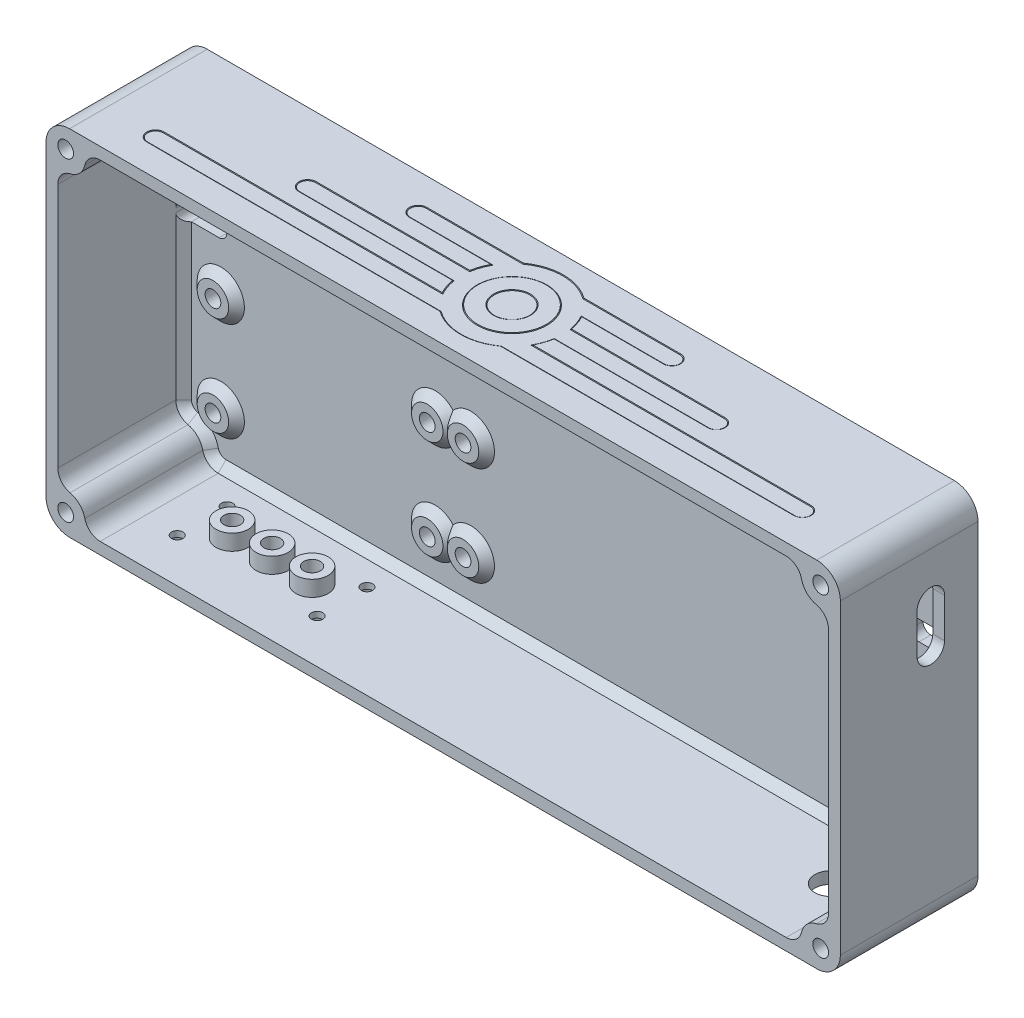
SolidWorks part; units mm, degrees
ref_plane "Plan de face" through (0, 0, 0) normal (0, 0, 1) x (1, 0, 0)
ref_plane "Plan de dessus" through (0, 0, 0) normal (0, 1, 0) x (1, 0, 0)
ref_plane "Plan de droite" through (0, 0, 0) normal (1, 0, 0) x (0, 0, -1)
sketch "Esquisse1" plane through (0, 0, 0) normal (0, 0, 1) x (1, 0, 0)
  line L1 (-95, 45) -> (95, 45)
  line L2 (-101, 39) -> (-101, -39)
  line L3 (-95, -45) -> (95, -45)
  line L4 (101, 39) -> (101, -39)
  line L5 (-101, 45) -> (101, -45) construction
  line L6 (-101, -45) -> (101, 45) construction
  line L7 (96, -40) -> (-96, -40) construction
  line L8 (96, -40) -> (96, 40) construction
  line L9 (96, 40) -> (-96, 40) construction
  line L10 (-96, -40) -> (-96, 40) construction
  line L11 (96, -40) -> (-96, 40) construction
  line L12 (96, 40) -> (-96, -40) construction
  arc A0 (95, -45) -> (101, -39) centre (95, -39) ccw
  arc A1 (95, 45) -> (101, 39) centre (95, 39) cw
  arc A2 (-101, -39) -> (-95, -45) centre (-95, -39) ccw
  arc A3 (-95, 45) -> (-101, 39) centre (-95, 39) ccw
  circle A4 centre (-96, 40) radius 2
  circle A5 centre (-96, -40) radius 2
  circle A6 centre (96, 40) radius 2
  circle A7 centre (96, -40) radius 2
  point P0 (0, 0)
  point P18 (0, 0)
  dimension "D3" = 6
  dimension "D6" = 4
  dimension "D1" = 202
  dimension "D2" = 90
  dimension "D4" = 192
  dimension "D5" = 80
extrude "Boss.-Extru.1" add sketch "Esquisse1" along normal blind 35
shell "Coque1" thickness 3 removed face at (98, 40, 35)
sketch "Esquisse9" plane through (0, 0, 0) normal (0, 0, -1) x (-1, 0, 0)
  circle A0 centre (96, 40) radius 2 construction
  circle A1 centre (96, -40) radius 2 construction
  circle A2 centre (-96, -40) radius 2 construction
  circle A3 centre (-96, 40) radius 2 construction
  circle A4 centre (96, 40) radius 2
  circle A5 centre (96, -40) radius 2
  circle A6 centre (-96, -40) radius 2
  circle A7 centre (-96, 40) radius 2
extrude "Boss.-Extru.3" add sketch "Esquisse9" against normal offset from surface (25 mm away) 10 up to face at (0, 0, 35)
sketch "Esquisse2" plane through (0, 0, 3) normal (0, 0, 1) x (1, 0, 0)
  line L0 (91.4174, 42) -> (-91.4174, 42) construction
  line L1 (92.6, -33.9) -> (-29, -33.9) construction
  line L2 (92.6, -33.9) -> (92.6, 32) construction
  line L3 (92.6, 32) -> (-29, 32) construction
  line L4 (-29, -33.9) -> (-29, 32) construction
  line L5 (-30, -33.9) -> (-92.6, -33.9) construction
  line L6 (-30, -33.9) -> (-30, 32) construction
  line L7 (-30, 32) -> (-92.6, 32) construction
  line L8 (-92.6, -33.9) -> (-92.6, 32) construction
  line L9 (88.55, -29.4) -> (-24.95, -29.4) construction
  line L10 (88.55, -29.4) -> (88.55, -4.2) construction
  line L11 (88.55, -4.2) -> (-24.95, -4.2) construction
  line L12 (-24.95, -29.4) -> (-24.95, -4.2) construction
  line L13 (-34.05, -29.4) -> (-88.55, -29.4) construction
  line L14 (-34.05, -29.4) -> (-34.05, -4.2) construction
  line L15 (-34.05, -4.2) -> (-88.55, -4.2) construction
  line L16 (-88.55, -29.4) -> (-88.55, -4.2) construction
  line L17 (0, 0) -> (92.6, 32) construction
  line L20 (-92.6, 32) -> (0, 0) construction
  circle A0 centre (88.55, -29.4) radius 4
  circle A1 centre (88.55, -4.2) radius 4
  circle A2 centre (-24.95, -4.2) radius 4
  circle A3 centre (-24.95, -29.4) radius 4
  circle A4 centre (-34.05, -29.4) radius 4
  circle A5 centre (-34.05, -4.2) radius 4
  circle A6 centre (-88.55, -4.2) radius 4
  circle A7 centre (-88.55, -29.4) radius 4
  point P18 (31.8, -33.9)
  point P19 (31.8, -29.4)
  point P20 (-61.3, -33.9)
  point P21 (-61.3, -29.4)
  dimension "D9" = 8
  dimension "D1" = 121.6
  dimension "D2" = 1
  dimension "D3" = 62.6
  dimension "D4" = 25.2
  dimension "D5" = 113.5
  dimension "D6" = 54.5
  dimension "D7" = 4.5
  dimension "D8" = 65.9
  dimension "D10" = 10
extrude "Boss.-Extru.2" add sketch "Esquisse2" along normal blind 2
sketch "Esquisse3" plane through (0, 0, 5) normal (0, 0, 1) x (1, 0, 0)
  circle A0 centre (88.55, -29.4) radius 2
  circle A1 centre (88.55, -4.2) radius 2
  circle A2 centre (-24.95, -4.2) radius 2
  circle A3 centre (-24.95, -29.4) radius 2
  circle A4 centre (-34.05, -29.4) radius 2
  circle A5 centre (-88.55, -4.2) radius 2
  circle A6 centre (-88.55, -29.4) radius 2
  circle A7 centre (-34.05, -4.2) radius 2
  dimension "D1" = 4
extrude "Enlèv. mat.-Extru.1" cut sketch "Esquisse3" against normal through all
sketch "Esquisse4" plane through (0, -45, 0) normal (0, -1, 0) x (1, 0, 0)
  line L0 (81, 35) -> (81, 0) construction
  line L1 (-95, 35) -> (95, 35) construction
  line L2 (-95, 0) -> (95, 0) construction
  line L4 (-101, 35) -> (-101, 0) construction
  line L5 (-78.78, 23.85) -> (-43.22, 23.85) construction
  line L6 (-78.78, 23.85) -> (-78.78, 11.15) construction
  line L7 (-78.78, 11.15) -> (-43.22, 11.15) construction
  line L8 (-43.22, 23.85) -> (-43.22, 11.15) construction
  line L9 (-78.78, 23.85) -> (-43.22, 11.15) construction
  line L10 (-78.78, 11.15) -> (-43.22, 23.85) construction
  line L14 (101, 35) -> (101, 0) construction
  circle A0 centre (81, 17.5) radius 4
  circle A1 centre (-71.16, 17.5) radius 2.1
  circle A2 centre (-61, 17.5) radius 2.1
  circle A3 centre (-50.84, 17.5) radius 2.1
  point P10 (-61, 17.5)
  dimension "D1" = 8
  dimension "D5" = 4.2
  dimension "D2" = 20
  dimension "D3" = 35.56
  dimension "D4" = 12.7
  dimension "D7" = 40
  dimension "D8" = 17.5
  dimension "D6" = 3
extrude "Enlèv. mat.-Extru.2" cut sketch "Esquisse4" against normal up to next
hole_wizard "Chambrage pour vis à six pans creux M2.51" positions "Esquisse5" profile "Esquisse6" counterbore size "M2.5" standard "ISO" end condition up to next
sketch "Esquisse5" plane through (0, -45, 0) normal (0, -1, 0) x (-1, 0, 0)
  point P0 (78.78, -23.85)
  point P3 (78.78, -11.15)
  point P6 (43.22, -23.85)
  point P9 (43.22, -11.15)
sketch "Esquisse6" plane through (-78.78, -45, 23.85) normal (1, 0, 0) x (0, 0, -1)
  line L0 (0, 0) -> (0, 3)
  line L1 (0, 3) -> (1.45, 3)
  line L3 (1.45, 3) -> (1.45, 1.5)
  line L4 (1.45, 1.5) -> (2.75, 1.5)
  line L5 (2.75, 1.5) -> (2.75, 0)
  line L7 (2.75, 0) -> (0, 0)
  line L11 (0, -6.35) -> (0, 107.95) construction
  dimension "Diamètre du perçage jusqu'au prochain" = 2.9
  dimension "Profondeur du perçage jusqu'au prochain" = 3
  dimension "Diamètre du chambrage" = 5.5
  dimension "Profondeur du chambrage" = 1.5
sketch "Esquisse7" plane through (0, -42, 0) normal (0, 1, 0) x (1, 0, 0)
  circle A0 centre (-71.16, -17.5) radius 2.1 construction
  circle A1 centre (-61, -17.5) radius 2.1 construction
  circle A2 centre (-50.84, -17.5) radius 2.1 construction
  circle A3 centre (-71.16, -17.5) radius 2.1
  circle A4 centre (-61, -17.5) radius 2.1
  circle A5 centre (-50.84, -17.5) radius 2.1
extrude "Extru.-Mince1" add sketch "Esquisse7" along normal blind 4 thin thin type one direction wall 2
fillet "Congé1" radius 4 8 edges at (-91.4174, -42, 19) (-98, -35.4174, 19) (91.4174, -42, 19) (98, -35.4174, 19) (98, 35.4174, 19) (91.4174, 42, 19) (-91.4174, 42, 19) (-98, 35.4174, 19)
chamfer "Chanfrein1" distance 2 angle 45 24 edges at (92.4645, -36.4645, 3) (0, -42, 3) (-92.4645, -36.4645, 3) (-98, 0, 3) (-92.4645, 36.4645, 3) (0, 42, 3) (92.4645, 36.4645, 3) (98, 0, 3) (92.55, -4.2, 3) (-20.95, -4.2, 3) (-20.95, -29.4, 3) (92.55, -29.4, 3) (-30.05, -29.4, 3) (-30.05, -4.2, 3) (-84.55, -4.2, 3) (-84.55, -29.4, 3) (-97.1269, -33.7195, 3) (-97.1269, 33.7195, 3) (-89.7195, 41.1269, 3) (89.7195, 41.1269, 3) (97.1269, 33.7195, 3) (97.1269, -33.7195, 3) (89.7195, -41.1269, 3) (-89.7195, -41.1269, 3)
sketch "Esquisse11" plane through (0, 0, 0) normal (0, 0, -1) x (-1, 0, 0)
  line L0 (-95, 45) -> (95, 45) construction
  line L1 (81, -25) -> (-81, -25) construction
  line L2 (81, -25) -> (81, 25) construction
  line L3 (81, 25) -> (-81, 25) construction
  line L4 (-81, -25) -> (-81, 25) construction
  line L5 (81, -25) -> (-81, 25) construction
  line L6 (81, 25) -> (-81, -25) construction
  line L7 (-83.6, 22.4) -> (-78.4, 22.4)
  line L8 (-83.6, 22.4) -> (-83.6, 27.6)
  line L9 (-83.6, 27.6) -> (-78.4, 27.6)
  line L10 (-78.4, 22.4) -> (-78.4, 27.6)
  line L11 (-83.6, 22.4) -> (-78.4, 27.6) construction
  line L12 (-83.6, 27.6) -> (-78.4, 22.4) construction
  line L13 (-83.6, -22.4) -> (-78.4, -22.4)
  line L14 (-83.6, -22.4) -> (-83.6, -27.6)
  line L15 (-83.6, -27.6) -> (-78.4, -27.6)
  line L16 (-78.4, -22.4) -> (-78.4, -27.6)
  line L17 (-83.6, -22.4) -> (-78.4, -27.6) construction
  line L18 (-83.6, -27.6) -> (-78.4, -22.4) construction
  line L19 (78.4, -22.4) -> (83.6, -22.4)
  line L20 (78.4, -22.4) -> (78.4, -27.6)
  line L21 (78.4, -27.6) -> (83.6, -27.6)
  line L22 (83.6, -22.4) -> (83.6, -27.6)
  line L23 (78.4, -22.4) -> (83.6, -27.6) construction
  line L24 (78.4, -27.6) -> (83.6, -22.4) construction
  line L25 (78.4, 27.6) -> (83.6, 27.6)
  line L26 (78.4, 27.6) -> (78.4, 22.4)
  line L27 (78.4, 22.4) -> (83.6, 22.4)
  line L28 (83.6, 27.6) -> (83.6, 22.4)
  line L29 (78.4, 27.6) -> (83.6, 22.4) construction
  line L30 (78.4, 22.4) -> (83.6, 27.6) construction
  line L31 (-101, -39) -> (-101, 39) construction
  point P0 (0, 0)
  dimension "D1" = 5.2
  dimension "D2" = 20
  dimension "D3" = 20
extrude "Enlèv. mat.-Extru.5" cut sketch "Esquisse11" against normal blind 2.5
sketch "Esquisse8" plane through (0, 0, 0) normal (0, 0, -1) x (-1, 0, 0)
  line L1 (-98, 42) -> (98, 42)
  line L2 (-98, 42) -> (-98, 31)
  line L3 (-98, 31) -> (98, 31)
  line L4 (98, 42) -> (98, 31)
  line L5 (-98, 42) -> (98, 31) construction
  line L6 (-98, 31) -> (98, 42) construction
  line L7 (-98, -35.4174) -> (-98, 44.5826) construction
  line L8 (98, 35.4174) -> (98, -44.5826) construction
  line L9 (87.225, 42) -> (-87.225, 42) construction
  line L11 (-98, 31) -> (-87, 31)
  line L12 (-98, 31) -> (-98, 8)
  line L13 (-98, 8) -> (-87, 8)
  line L14 (-87, 31) -> (-87, 8)
  line L15 (98, 31) -> (87, 31)
  line L16 (98, 31) -> (98, 8)
  line L17 (98, 8) -> (87, 8)
  line L18 (87, 31) -> (87, 8)
  point P0 (0, 36.5)
  dimension "D1" = 23
  dimension "D2" = 11
extrude "Enlèv. mat.-Extru.3" cut sketch "Esquisse8" against normal blind 2 contours L14 L3 L12 L13 | L4 L1 L2 L3 | L3 L18 L17 L16 region at (0, 36.5, 0) region at (92.5, 19.5, 0) region at (-92.5, 19.5, 0)
sketch "Esquisse10" plane through (0, 0, 2) normal (0, 0, -1) x (-1, 0, 0)
  line L10 (-87, 31) -> (-87, 8) construction
  line L11 (-98, 8) -> (-87, 8)
  line L12 (-98, 8) -> (-98, 13)
  line L13 (-98, 13) -> (-87, 13)
  line L14 (-87, 8) -> (-87, 13)
  line L15 (87, 31) -> (87, 8) construction
  line L16 (98, 8) -> (87, 8)
  line L17 (98, 8) -> (98, 13)
  line L18 (98, 13) -> (87, 13)
  line L19 (87, 8) -> (87, 13)
  dimension "D1" = 5
extrude "Enlèv. mat.-Extru.4" cut sketch "Esquisse10" against normal up to next
fillet "Congé2" radius 2 12 edges at (-98, 8, 2.5) (-98, 13, 3.5) (-87, 13, 2.5) (-87, 8, 1.5) (-87, 31, 1) (-98, 42, 1) (98, 8, 2.5) (98, 13, 3.5) (87, 13, 2.5) (98, 42, 1) (87, 8, 1.5) (87, 31, 1)
sketch "Esquisse15" plane through (0, 45, 0) normal (0, 1, 0) x (1, 0, 0)
  line L0 (0, 0) -> (0, -35) construction
  line L1 (95, 0) -> (-95, 0) construction
  line L2 (95, -35) -> (-95, -35) construction
  line L3 (-8.7, -17.5) -> (-51.9785, -17.5) construction
  line L4 (-8.7, -19.7) -> (-51.9785, -19.7)
  line L5 (-8.7, -15.3) -> (-51.9785, -15.3)
  line L6 (-2.265, -9.1) -> (-32.265, -9.1) construction
  line L7 (-2.265, -11.3) -> (-32.265, -11.3)
  line L8 (-2.265, -6.9) -> (-32.265, -6.9)
  line L9 (-2.265, -25.9) -> (-82.265, -25.9) construction
  line L10 (-2.265, -28.1) -> (-82.265, -28.1)
  line L11 (-2.265, -23.7) -> (-82.265, -23.7)
  circle A0 centre (0, -17.5) radius 4.7
  circle A1 centre (0, -17.5) radius 8.7
  circle A2 centre (0, -17.5) radius 13.1
  arc A3 (-8.7, -19.7) -> (-8.7, -15.3) centre (-8.7, -17.5) ccw
  arc A4 (-51.9785, -15.3) -> (-51.9785, -19.7) centre (-51.9785, -17.5) ccw
  arc A5 (-2.265, -11.3) -> (-2.265, -6.9) centre (-2.265, -9.1) ccw
  arc A6 (-32.265, -6.9) -> (-32.265, -11.3) centre (-32.265, -9.1) ccw
  arc A7 (-2.265, -28.1) -> (-2.265, -23.7) centre (-2.265, -25.9) ccw
  arc A8 (-82.265, -23.7) -> (-82.265, -28.1) centre (-82.265, -25.9) ccw
  arc A15 (-32.265, -9.1) -> (-82.265, -25.9) centre (-120.4091, 170.4289) cw construction
  point P14 (-30.3393, -17.5)
  point P19 (-17.265, -9.1)
  point P26 (-42.265, -25.9)
  dimension "D2" = 9.4
  dimension "D3" = 4
  dimension "D4" = 4.4
  dimension "D5" = 2.2
  dimension "D9" = 200
  dimension "D1" = 8.4
  dimension "D6" = 8.4
  dimension "D7" = 30
  dimension "D8" = 80
extrude "Enlèv. mat.-Extru.7" cut sketch "Esquisse15" against normal blind 1.6 contours A7 L10 A2 L8 A5 A1 | L10 A7 A1 L11 A2 | L11 A8 L10 A2 | A3 L4 A2 L11 A1 | L5 A4 L4 A2 | L4 A3 A1 L5 A2 | A3 A1 L7 A2 L5 | A1 A5 L8 A2 L7 | L8 A6 L7 A2 | A0 region at (-9.8958, 45, 21.7619) region at (-10.8222, 45, 17.5) region at (-33.3752, 45, 17.5) region at (-9.8958, 45, 13.2381) region at (-46.9456, 45, 25.9187) region at (-6.0605, 45, 26.0393) region at (-6.0605, 45, 8.9607) region at (-21.9321, 45, 9.0425) region at (-4.9812, 45, 28.4345) region at (0, 45, 17.5)
mirror "Symétrie1" about plane through (0, 0, 0) normal (1, 0, 0) of "Enlèv. mat.-Extru.7"
sketch "Esquisse16" plane through (0, 43.4, 0) normal (0, 1, 0) x (1, 0, 0)
  line L25 (-11.2004, -23.9) -> (-82.265, -23.9)
  line L26 (-82.265, -27.9) -> (-7.6322, -27.9)
  line L27 (7.6322, -27.9) -> (82.265, -27.9)
  line L28 (82.265, -23.9) -> (11.2004, -23.9)
  line L29 (12.744, -19.5) -> (51.9785, -19.5)
  line L30 (51.9785, -15.5) -> (12.744, -15.5)
  line L31 (11.2004, -11.1) -> (32.265, -11.1)
  line L32 (32.265, -7.1) -> (7.6322, -7.1)
  line L33 (-7.6322, -7.1) -> (-32.265, -7.1)
  line L34 (-32.265, -11.1) -> (-11.2004, -11.1)
  line L35 (-12.744, -15.5) -> (-51.9785, -15.5)
  line L36 (-51.9785, -19.5) -> (-12.744, -19.5)
  line L37 (-11.2004, -23.9) -> (-82.265, -23.9)
  line L38 (-82.265, -27.9) -> (-7.6322, -27.9)
  line L39 (7.6322, -27.9) -> (82.265, -27.9)
  line L40 (82.265, -23.9) -> (11.2004, -23.9)
  line L41 (12.744, -19.5) -> (51.9785, -19.5)
  line L42 (51.9785, -15.5) -> (12.744, -15.5)
  line L43 (11.2004, -11.1) -> (32.265, -11.1)
  line L44 (32.265, -7.1) -> (7.6322, -7.1)
  line L45 (-7.6322, -7.1) -> (-32.265, -7.1)
  line L46 (-32.265, -11.1) -> (-11.2004, -11.1)
  line L47 (-12.744, -15.5) -> (-51.9785, -15.5)
  line L48 (-51.9785, -19.5) -> (-12.744, -19.5)
  circle A16 centre (0, -17.5) radius 8.9
  circle A17 centre (0, -17.5) radius 8.9
  circle A19 centre (0, -17.5) radius 4.5
  circle A20 centre (0, -17.5) radius 4.5
  arc A26 (-12.744, -19.5) -> (-11.2004, -23.9) centre (0, -17.5) ccw
  arc A27 (-82.265, -23.9) -> (-82.265, -27.9) centre (-82.265, -25.9) ccw
  arc A28 (-7.6322, -27.9) -> (7.6322, -27.9) centre (0, -17.5) ccw
  arc A29 (82.265, -27.9) -> (82.265, -23.9) centre (82.265, -25.9) ccw
  arc A30 (11.2004, -23.9) -> (12.744, -19.5) centre (0, -17.5) ccw
  arc A31 (51.9785, -19.5) -> (51.9785, -15.5) centre (51.9785, -17.5) ccw
  arc A32 (12.744, -15.5) -> (11.2004, -11.1) centre (0, -17.5) ccw
  arc A33 (32.265, -11.1) -> (32.265, -7.1) centre (32.265, -9.1) ccw
  arc A34 (7.6322, -7.1) -> (-7.6322, -7.1) centre (0, -17.5) ccw
  arc A35 (-32.265, -7.1) -> (-32.265, -11.1) centre (-32.265, -9.1) ccw
  arc A36 (-11.2004, -11.1) -> (-12.744, -15.5) centre (0, -17.5) ccw
  arc A37 (-51.9785, -15.5) -> (-51.9785, -19.5) centre (-51.9785, -17.5) ccw
  arc A38 (-12.744, -19.5) -> (-11.2004, -23.9) centre (0, -17.5) ccw
  arc A39 (-82.265, -23.9) -> (-82.265, -27.9) centre (-82.265, -25.9) ccw
  arc A40 (-7.6322, -27.9) -> (7.6322, -27.9) centre (0, -17.5) ccw
  arc A41 (82.265, -27.9) -> (82.265, -23.9) centre (82.265, -25.9) ccw
  arc A42 (11.2004, -23.9) -> (12.744, -19.5) centre (0, -17.5) ccw
  arc A43 (51.9785, -19.5) -> (51.9785, -15.5) centre (51.9785, -17.5) ccw
  arc A44 (12.744, -15.5) -> (11.2004, -11.1) centre (0, -17.5) ccw
  arc A45 (32.265, -11.1) -> (32.265, -7.1) centre (32.265, -9.1) ccw
  arc A46 (7.6322, -7.1) -> (-7.6322, -7.1) centre (0, -17.5) ccw
  arc A47 (-32.265, -7.1) -> (-32.265, -11.1) centre (-32.265, -9.1) ccw
  arc A48 (-11.2004, -11.1) -> (-12.744, -15.5) centre (0, -17.5) ccw
  arc A49 (-51.9785, -15.5) -> (-51.9785, -19.5) centre (-51.9785, -17.5) ccw
  dimension "D1" = 0.2
  dimension "D2" = 0.2
  dimension "D3" = 0.2
extrude "Boss.-Extru.6" add sketch "Esquisse16" along normal blind 1.5 separate body contours L47 A49 L48 A38 L37 A39 L38 A40 L39 A41 L40 A42 L41 A43 L42 A44 L43 A45 L44 A46 L45 A47 L46 A48 A17 | A20 region at (-10.5639, 43.4, 21.2059) region at (0, 43.4, 17.5)
sketch "Esquisse17" plane through (0, 42, 0) normal (0, -1, 0) x (1, 0, 0)
  line L0 (-6.2, 23.7) -> (6.2, 23.7)
  line L1 (-6, 23.5) -> (6, 23.5) construction
  line L2 (-6, 23.5) -> (-6, 11.5) construction
  line L3 (-6, 11.5) -> (6, 11.5) construction
  line L4 (6, 23.5) -> (6, 11.5) construction
  line L5 (-6, 23.5) -> (6, 11.5) construction
  line L6 (-6, 11.5) -> (6, 23.5) construction
  line L7 (6.2, 23.7) -> (6.2, 11.3)
  line L8 (-6.2, 11.3) -> (6.2, 11.3)
  line L9 (-6.2, 23.7) -> (-6.2, 11.3)
  line L10 (-8.2, 25.7) -> (8.2, 25.7)
  line L11 (8.2, 25.7) -> (8.2, 9.3)
  line L12 (-8.2, 9.3) -> (8.2, 9.3)
  line L13 (-8.2, 25.7) -> (-8.2, 9.3)
  circle A0 centre (0, 17.5) radius 4.7 construction
  circle A1 centre (0, 17.5) radius 3.5 construction
  circle A2 centre (0, 17.5) radius 3.9
  point P0 (0, 17.5)
  dimension "D2" = 7
  dimension "D1" = 12
  dimension "D3" = 0.2
  dimension "D4" = 2
  dimension "D5" = 0.4
extrude "Boss.-Extru.7" add sketch "Esquisse17" along normal blind 2.3 contours L0 L9 L8 L7 A2 | L10 L13 L12 L11 L9 L0 L7 L8 region at (0, 42, 23.5246) region at (0, 42, 25.4681)
extrude "Boss.-Extru.8" add sketch "Esquisse17<3>" along normal blind 3 from surface contours L10 L13 L12 L11 L9 L0 L7 L8 region at (0, 42, 25.4681) starting at face at (0, 39.7, 13.6)
sketch "Esquisse17<3>" plane through (0, 42, 0) normal (0, -1, 0) x (1, 0, 0) same geometry as "Esquisse17"
extrude "Enlèv. mat.-Extru.8" cut sketch "Esquisse17<4>" against normal up to next (1.4 mm away) contours A2
sketch "Esquisse17<4>" plane through (0, 42, 0) normal (0, -1, 0) x (1, 0, 0) same geometry as "Esquisse17"
sketch "Esquisse18" plane through (0, 43.4, 0) normal (0, -1, 0) x (1, 0, 0)
  circle A2 centre (0, 17.5) radius 4.7 construction
  circle A3 centre (0, 17.5) radius 4.7
extrude "Enlèv. mat.-Extru.9" cut sketch "Esquisse18" along normal blind 2
chamfer "Chanfrein2" distance 5.3 angle 45 3 edges at (-8.2, 42, 17.5) (0, 42, 25.7) (8.2, 42, 17.5)
sketch "Esquisse19" plane through (0, 0, 11.3) normal (0, 0, 1) x (1, 0, 0)
  line L4 (13.5, 42) -> (-13.5, 42)
  line L5 (8.2, 36.7) -> (13.5, 42)
  line L6 (-8.2, 36.7) -> (8.2, 36.7)
  line L7 (-13.5, 42) -> (-8.2, 36.7)
  line L8 (13.5, 42) -> (-13.5, 42)
  line L9 (8.2, 36.7) -> (13.5, 42)
  line L10 (-8.2, 36.7) -> (8.2, 36.7)
  line L11 (-13.5, 42) -> (-8.2, 36.7)
  dimension "D1" = 0
extrude "Boss.-Extru.9" add sketch "Esquisse19" against normal up to surface (8.3 mm away) up to face at (0.0211, -1.7773, 3)
sketch "Esquisse20" plane through (-6.2, 0, 0) normal (1, 0, 0) x (0, 0, -1)
  line L0 (-11.3, 36.7) -> (-23.7, 36.7) construction
  line L1 (-15, 36.7) -> (-20, 36.7) construction
  circle A0 centre (-20, 36.7) radius 1
  circle A1 centre (-15, 36.7) radius 1
  point P6 (-17.5, 36.7)
  dimension "D2" = 2
  dimension "D1" = 5
extrude "Enlèv. mat.-Extru.10" cut sketch "Esquisse20" against normal up to surface and the other way up to surface up to face at (-10.98, 39.48, 13.54) other way up to face at (10.98, 39.48, 13.54)
sketch "Esquisse21" plane through (101, 0, 0) normal (1, 0, 0) x (0, 0, -1)
  line L0 (-12, 17) -> (-12, 27) construction
  line L1 (-15.5, 17) -> (-15.5, 27)
  line L2 (-8.5, 17) -> (-8.5, 27)
  line L3 (0, -39) -> (0, 39) construction
  arc A0 (-15.5, 17) -> (-8.5, 17) centre (-12, 17) ccw
  arc A1 (-8.5, 27) -> (-15.5, 27) centre (-12, 27) ccw
  point P2 (-12, 22)
  dimension "D1" = 7
  dimension "D2" = 10
  dimension "D3" = 12
  dimension "D4" = 22
extrude "Enlèv. mat.-Extru.11" cut sketch "Esquisse21" against normal up to next (3 mm away)
